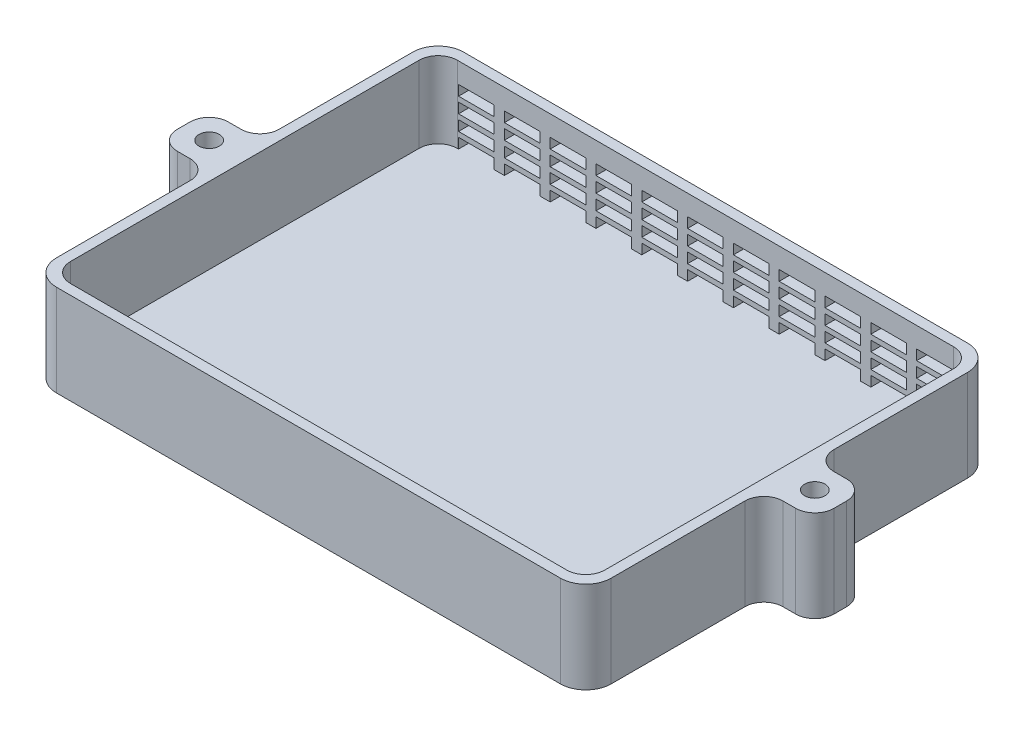
SolidWorks part; units mm, degrees
ref_plane "Front Plane" through (0, 0, 0) normal (0, 0, 1) x (1, 0, 0)
ref_plane "Top Plane" through (0, 0, 0) normal (0, 1, 0) x (1, 0, 0)
ref_plane "Right Plane" through (0, 0, 0) normal (1, 0, 0) x (0, 0, -1)
sketch "Sketch1" plane through (0, 0, 0) normal (0, 1, 0) x (1, 0, 0)
  line L1 (0, 0) -> (87.2, 0)
  line L2 (0, 0) -> (0, -64)
  line L3 (0, -64) -> (87.2, -64)
  line L4 (87.2, 0) -> (87.2, -64)
  dimension "D1" = 64
  dimension "D2" = 87.2
extrude "Boss-Extrude1" add sketch "Sketch1" along normal blind 2.4
sketch "Sketch2" plane through (0, 2.4, 0) normal (0, 1, 0) x (1, 0, 0)
  line L0 (85.6, -62.4) -> (85.6, -1.6)
  line L1 (87.2, -64) -> (0, -64)
  line L2 (87.2, -64) -> (87.2, 0)
  line L3 (87.2, 0) -> (0, 0)
  line L4 (0, -64) -> (0, 0)
  line L5 (85.6, -1.6) -> (1.6, -1.6)
  line L6 (1.6, -62.4) -> (1.6, -1.6)
  line L7 (85.6, -62.4) -> (1.6, -62.4)
  dimension "D1" = 1.6
extrude "Boss-Extrude2" add sketch "Sketch2" along normal blind 12
sketch "Sketch4" plane through (0, 0, 0) normal (0, 0, -1) x (-1, 0, 0)
  line L0 (-87.2, 0) -> (0, 0) construction
  line L1 (-4.8, 4) -> (-10.4, 4)
  line L2 (-4.8, 4) -> (-4.8, 2.4)
  line L3 (-4.8, 2.4) -> (-10.4, 2.4)
  line L4 (-10.4, 4) -> (-10.4, 2.4)
  line L5 (0, 14.4) -> (0, 0) construction
  line L6 (-12, 2.4) -> (-17.6, 2.4)
  line L7 (-17.6, 4) -> (-17.6, 2.4)
  line L8 (-12, 4) -> (-17.6, 4)
  line L9 (-12, 4) -> (-12, 2.4)
  line L10 (-19.2, 2.4) -> (-24.8, 2.4)
  line L11 (-24.8, 4) -> (-24.8, 2.4)
  line L12 (-19.2, 4) -> (-24.8, 4)
  line L13 (-19.2, 4) -> (-19.2, 2.4)
  line L14 (-26.4, 2.4) -> (-32, 2.4)
  line L15 (-32, 4) -> (-32, 2.4)
  line L16 (-26.4, 4) -> (-32, 4)
  line L17 (-26.4, 4) -> (-26.4, 2.4)
  line L18 (-33.6, 2.4) -> (-39.2, 2.4)
  line L19 (-39.2, 4) -> (-39.2, 2.4)
  line L20 (-33.6, 4) -> (-39.2, 4)
  line L21 (-33.6, 4) -> (-33.6, 2.4)
  line L22 (-40.8, 2.4) -> (-46.4, 2.4)
  line L23 (-46.4, 4) -> (-46.4, 2.4)
  line L24 (-40.8, 4) -> (-46.4, 4)
  line L25 (-40.8, 4) -> (-40.8, 2.4)
  line L26 (-48, 2.4) -> (-53.6, 2.4)
  line L27 (-53.6, 4) -> (-53.6, 2.4)
  line L28 (-48, 4) -> (-53.6, 4)
  line L29 (-48, 4) -> (-48, 2.4)
  line L30 (-55.2, 2.4) -> (-60.8, 2.4)
  line L31 (-60.8, 4) -> (-60.8, 2.4)
  line L32 (-55.2, 4) -> (-60.8, 4)
  line L33 (-55.2, 4) -> (-55.2, 2.4)
  line L34 (-12, 4.8) -> (-17.6, 4.8)
  line L35 (-17.6, 6.4) -> (-17.6, 4.8)
  line L36 (-12, 6.4) -> (-17.6, 6.4)
  line L37 (-12, 6.4) -> (-12, 4.8)
  line L38 (-19.2, 4.8) -> (-24.8, 4.8)
  line L39 (-24.8, 6.4) -> (-24.8, 4.8)
  line L40 (-19.2, 6.4) -> (-24.8, 6.4)
  line L41 (-19.2, 6.4) -> (-19.2, 4.8)
  line L42 (-26.4, 4.8) -> (-32, 4.8)
  line L43 (-32, 6.4) -> (-32, 4.8)
  line L44 (-26.4, 6.4) -> (-32, 6.4)
  line L45 (-26.4, 6.4) -> (-26.4, 4.8)
  line L46 (-33.6, 4.8) -> (-39.2, 4.8)
  line L47 (-39.2, 6.4) -> (-39.2, 4.8)
  line L48 (-33.6, 6.4) -> (-39.2, 6.4)
  line L49 (-33.6, 6.4) -> (-33.6, 4.8)
  line L50 (-40.8, 4.8) -> (-46.4, 4.8)
  line L51 (-46.4, 6.4) -> (-46.4, 4.8)
  line L52 (-40.8, 6.4) -> (-46.4, 6.4)
  line L53 (-40.8, 6.4) -> (-40.8, 4.8)
  line L54 (-48, 4.8) -> (-53.6, 4.8)
  line L55 (-53.6, 6.4) -> (-53.6, 4.8)
  line L56 (-48, 6.4) -> (-53.6, 6.4)
  line L57 (-48, 6.4) -> (-48, 4.8)
  line L58 (-55.2, 4.8) -> (-60.8, 4.8)
  line L59 (-60.8, 6.4) -> (-60.8, 4.8)
  line L60 (-55.2, 6.4) -> (-60.8, 6.4)
  line L61 (-55.2, 6.4) -> (-55.2, 4.8)
  line L62 (-12, 7.2) -> (-17.6, 7.2)
  line L63 (-17.6, 8.8) -> (-17.6, 7.2)
  line L64 (-12, 8.8) -> (-17.6, 8.8)
  line L65 (-12, 8.8) -> (-12, 7.2)
  line L66 (-19.2, 7.2) -> (-24.8, 7.2)
  line L67 (-24.8, 8.8) -> (-24.8, 7.2)
  line L68 (-19.2, 8.8) -> (-24.8, 8.8)
  line L69 (-19.2, 8.8) -> (-19.2, 7.2)
  line L70 (-26.4, 7.2) -> (-32, 7.2)
  line L71 (-32, 8.8) -> (-32, 7.2)
  line L72 (-26.4, 8.8) -> (-32, 8.8)
  line L73 (-26.4, 8.8) -> (-26.4, 7.2)
  line L74 (-33.6, 7.2) -> (-39.2, 7.2)
  line L75 (-39.2, 8.8) -> (-39.2, 7.2)
  line L76 (-33.6, 8.8) -> (-39.2, 8.8)
  line L77 (-33.6, 8.8) -> (-33.6, 7.2)
  line L78 (-40.8, 7.2) -> (-46.4, 7.2)
  line L79 (-46.4, 8.8) -> (-46.4, 7.2)
  line L80 (-40.8, 8.8) -> (-46.4, 8.8)
  line L81 (-40.8, 8.8) -> (-40.8, 7.2)
  line L82 (-48, 7.2) -> (-53.6, 7.2)
  line L83 (-53.6, 8.8) -> (-53.6, 7.2)
  line L84 (-48, 8.8) -> (-53.6, 8.8)
  line L85 (-48, 8.8) -> (-48, 7.2)
  line L86 (-55.2, 7.2) -> (-60.8, 7.2)
  line L87 (-60.8, 8.8) -> (-60.8, 7.2)
  line L88 (-55.2, 8.8) -> (-60.8, 8.8)
  line L89 (-55.2, 8.8) -> (-55.2, 7.2)
  line L90 (-4.8, 4.8) -> (-10.4, 4.8)
  line L91 (-10.4, 6.4) -> (-10.4, 4.8)
  line L92 (-4.8, 6.4) -> (-10.4, 6.4)
  line L93 (-4.8, 6.4) -> (-4.8, 4.8)
  line L94 (-4.8, 7.2) -> (-10.4, 7.2)
  line L95 (-10.4, 8.8) -> (-10.4, 7.2)
  line L96 (-4.8, 8.8) -> (-10.4, 8.8)
  line L97 (-4.8, 8.8) -> (-4.8, 7.2)
  line L98 (-4.8, 9.6) -> (-10.4, 9.6)
  line L99 (-10.4, 11.2) -> (-10.4, 9.6)
  line L100 (-4.8, 11.2) -> (-10.4, 11.2)
  line L101 (-4.8, 11.2) -> (-4.8, 9.6)
  line L102 (-12, 9.6) -> (-17.6, 9.6)
  line L103 (-17.6, 11.2) -> (-17.6, 9.6)
  line L104 (-12, 11.2) -> (-17.6, 11.2)
  line L105 (-12, 11.2) -> (-12, 9.6)
  line L106 (-19.2, 9.6) -> (-24.8, 9.6)
  line L107 (-24.8, 11.2) -> (-24.8, 9.6)
  line L108 (-19.2, 11.2) -> (-24.8, 11.2)
  line L109 (-19.2, 11.2) -> (-19.2, 9.6)
  line L110 (-26.4, 9.6) -> (-32, 9.6)
  line L111 (-32, 11.2) -> (-32, 9.6)
  line L112 (-26.4, 11.2) -> (-32, 11.2)
  line L113 (-26.4, 11.2) -> (-26.4, 9.6)
  line L114 (-33.6, 9.6) -> (-39.2, 9.6)
  line L115 (-39.2, 11.2) -> (-39.2, 9.6)
  line L116 (-33.6, 11.2) -> (-39.2, 11.2)
  line L117 (-33.6, 11.2) -> (-33.6, 9.6)
  line L118 (-40.8, 9.6) -> (-46.4, 9.6)
  line L119 (-46.4, 11.2) -> (-46.4, 9.6)
  line L120 (-40.8, 11.2) -> (-46.4, 11.2)
  line L121 (-40.8, 11.2) -> (-40.8, 9.6)
  line L122 (-48, 9.6) -> (-53.6, 9.6)
  line L123 (-53.6, 11.2) -> (-53.6, 9.6)
  line L124 (-48, 11.2) -> (-53.6, 11.2)
  line L125 (-48, 11.2) -> (-48, 9.6)
  line L126 (-55.2, 9.6) -> (-60.8, 9.6)
  line L127 (-60.8, 11.2) -> (-60.8, 9.6)
  line L128 (-55.2, 11.2) -> (-60.8, 11.2)
  line L129 (-55.2, 11.2) -> (-55.2, 9.6)
  line L130 (-62.4, 2.4) -> (-68, 2.4)
  line L131 (-68, 4) -> (-68, 2.4)
  line L132 (-62.4, 4) -> (-68, 4)
  line L133 (-62.4, 4) -> (-62.4, 2.4)
  line L134 (-69.6, 2.4) -> (-75.2, 2.4)
  line L135 (-75.2, 4) -> (-75.2, 2.4)
  line L136 (-69.6, 4) -> (-75.2, 4)
  line L137 (-69.6, 4) -> (-69.6, 2.4)
  line L138 (-76.8, 2.4) -> (-82.4, 2.4)
  line L139 (-82.4, 4) -> (-82.4, 2.4)
  line L140 (-76.8, 4) -> (-82.4, 4)
  line L141 (-76.8, 4) -> (-76.8, 2.4)
  line L146 (-62.4, 4.8) -> (-68, 4.8)
  line L147 (-68, 6.4) -> (-68, 4.8)
  line L148 (-62.4, 6.4) -> (-68, 6.4)
  line L149 (-62.4, 6.4) -> (-62.4, 4.8)
  line L150 (-69.6, 4.8) -> (-75.2, 4.8)
  line L151 (-75.2, 6.4) -> (-75.2, 4.8)
  line L152 (-69.6, 6.4) -> (-75.2, 6.4)
  line L153 (-69.6, 6.4) -> (-69.6, 4.8)
  line L154 (-76.8, 4.8) -> (-82.4, 4.8)
  line L155 (-82.4, 6.4) -> (-82.4, 4.8)
  line L156 (-76.8, 6.4) -> (-82.4, 6.4)
  line L157 (-76.8, 6.4) -> (-76.8, 4.8)
  line L162 (-62.4, 7.2) -> (-68, 7.2)
  line L163 (-68, 8.8) -> (-68, 7.2)
  line L164 (-62.4, 8.8) -> (-68, 8.8)
  line L165 (-62.4, 8.8) -> (-62.4, 7.2)
  line L166 (-69.6, 7.2) -> (-75.2, 7.2)
  line L167 (-75.2, 8.8) -> (-75.2, 7.2)
  line L168 (-69.6, 8.8) -> (-75.2, 8.8)
  line L169 (-69.6, 8.8) -> (-69.6, 7.2)
  line L170 (-76.8, 7.2) -> (-82.4, 7.2)
  line L171 (-82.4, 8.8) -> (-82.4, 7.2)
  line L172 (-76.8, 8.8) -> (-82.4, 8.8)
  line L173 (-76.8, 8.8) -> (-76.8, 7.2)
  line L178 (-62.4, 9.6) -> (-68, 9.6)
  line L179 (-68, 11.2) -> (-68, 9.6)
  line L180 (-62.4, 11.2) -> (-68, 11.2)
  line L181 (-62.4, 11.2) -> (-62.4, 9.6)
  line L182 (-69.6, 9.6) -> (-75.2, 9.6)
  line L183 (-75.2, 11.2) -> (-75.2, 9.6)
  line L184 (-69.6, 11.2) -> (-75.2, 11.2)
  line L185 (-69.6, 11.2) -> (-69.6, 9.6)
  line L186 (-76.8, 9.6) -> (-82.4, 9.6)
  line L187 (-82.4, 11.2) -> (-82.4, 9.6)
  line L188 (-76.8, 11.2) -> (-82.4, 11.2)
  line L189 (-76.8, 11.2) -> (-76.8, 9.6)
  dimension "D1" = 5.6
  dimension "D2" = 1.6
  dimension "D3" = 2.4
  dimension "D4" = 4.8
  dimension "D5" = 11
  dimension "D6" = 4
extrude "Cut-Extrude1" cut sketch "Sketch4" against normal blind 12
sketch "Sketch7" plane through (0, 14.4, 0) normal (0, 1, 0) x (1, 0, 0)
  line L0 (87.2, -64) -> (87.2, 0) construction
  line L1 (87.2, -36) -> (95.2, -36)
  line L2 (87.2, -36) -> (87.2, -28)
  line L3 (87.2, -28) -> (95.2, -28)
  line L4 (95.2, -36) -> (95.2, -28)
  line L5 (43.6, -64) -> (43.6, -51.727) construction
  line L6 (0, -64) -> (87.2, -64) construction
  line L7 (0, -36) -> (0, -28)
  line L8 (0, -36) -> (-8, -36)
  line L9 (0, -28) -> (-8, -28)
  line L10 (-8, -36) -> (-8, -28)
  circle A0 centre (91.2, -32) radius 1.6
  circle A1 centre (-4, -32) radius 1.6
  dimension "D4" = 3.2
  dimension "D5" = 4
  dimension "D1" = 8
  dimension "D2" = 8
  dimension "D3" = 28
  dimension "D6" = 4
extrude "Boss-Extrude4" add sketch "Sketch7" against normal blind 14.4
fillet "Fillet3" radius 3 4 edges at (85.6, 8.4, 1.6) (1.6, 8.4, 1.6) (1.6, 8.4, 62.4) (85.6, 8.4, 62.4)
fillet "Fillet4" radius 4 4 edges at (87.2, 7.2, 0) (0, 7.2, 0) (0, 7.2, 64) (87.2, 7.2, 64)
fillet "Fillet8" radius 3 8 edges at (87.2, 7.2, 28) (87.2, 7.2, 36) (0, 7.2, 28) (0, 7.2, 36) (-8, 7.2, 28) (-8, 7.2, 36) (95.2, 7.2, 28) (95.2, 7.2, 36)
fillet "Fillet9" radius 1.6 2 edges at (91.2, 0, 33.6) (-4, 0, 30.4) conic rho 0.05
equation "\"D2@Sketch1\"=0.8*120-11.2+2.4"
